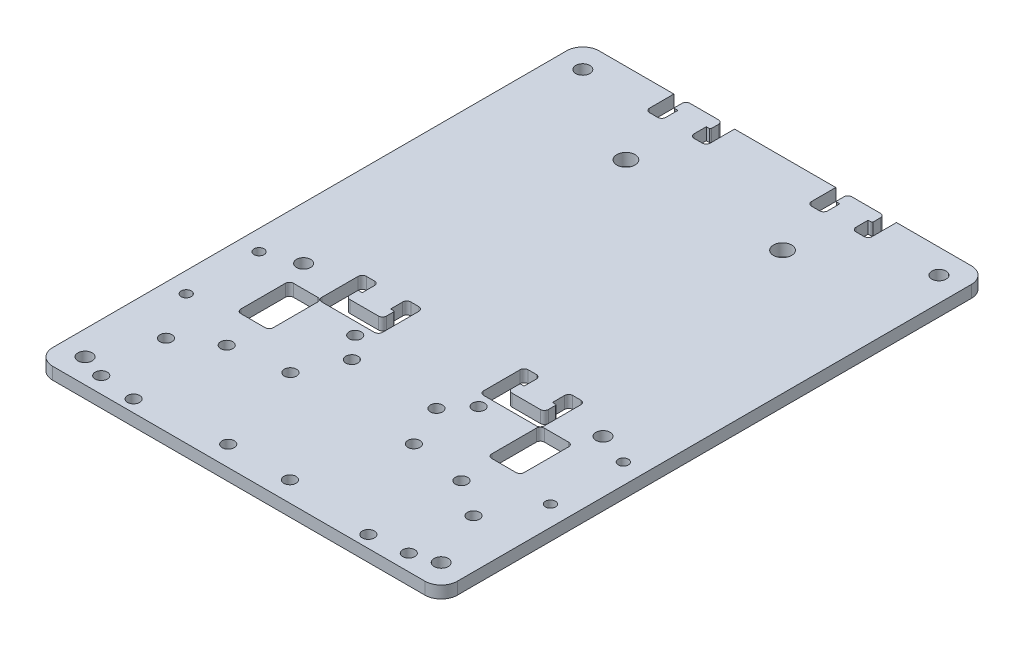
SolidWorks part; units mm, degrees
material "Acrylic (Medium-high impact)"
ref_plane "Front Plane" through (0, 0, 0) normal (0, 0, 1) x (1, 0, 0)
ref_plane "Top Plane" through (0, 0, 0) normal (0, 1, 0) x (1, 0, 0)
ref_plane "Right Plane" through (0, 0, 0) normal (1, 0, 0) x (0, 0, -1)
sketch "Sketch1" plane through (0, 0, 0) normal (0, 1, 0) x (1, 0, 0)
  line L1 (-50, 67.5) -> (50, 67.5)
  line L2 (-50, 67.5) -> (-50, -67.5)
  line L3 (-50, -67.5) -> (50, -67.5)
  line L4 (50, 67.5) -> (50, -67.5)
  line L5 (-50, 67.5) -> (50, -67.5) construction
  line L6 (-50, -67.5) -> (50, 67.5) construction
  point P0 (0, 0)
  dimension "D1" = 100
  dimension "D2" = 135
extrude "Stock" add sketch "Sketch1" against normal blind 3
fillet "base-rounds" radius 4 4 edges at (50, -1.5, 67.5) (50, -1.5, -67.5) (-50, -1.5, -67.5) (-50, -1.5, 67.5)
sketch "Sketch2" plane through (0, 0, 0) normal (0, 1, 0) x (1, 0, 0)
  line L0 (0, 0) -> (0, -62.6413) construction
  line L1 (0, 0) -> (-57.1686, 0) construction
  line L2 (-50, 63.5) -> (-50, -63.5) construction
  line L3 (-46, -67.5) -> (46, -67.5) construction
  circle A0 centre (-44, -61.5) radius 1.75
  circle A1 centre (-44, 61.5) radius 1.75
  circle A2 centre (44, -61.5) radius 1.75
  circle A3 centre (44, 61.5) radius 1.75
  circle A4 centre (-37, -14.5) radius 1.75
  circle A5 centre (37, -14.5) radius 1.75
  dimension "D3" = 3.5
  dimension "D1" = 6
  dimension "D2" = 6
  dimension "D4" = 76
  dimension "D5" = 37
extrude "holes-layers" cut sketch "Sketch2" against normal through all
sketch "Sketch4" plane through (0, 0, 0) normal (0, 1, 0) x (1, 0, 0)
  line L0 (0, 0) -> (0, -44.6235) construction
  line L5 (-46, -67.5) -> (46, -67.5) construction
  line L8 (-38, -63.5) -> (-38, -40.5) construction
  circle A0 centre (-38, -63.5) radius 1.5
  circle A1 centre (-38, -47.5) radius 1.5
  circle A4 centre (38, -47.5) radius 1.5
  circle A5 centre (38, -63.5) radius 1.5
  dimension "D2" = 3
  dimension "D1" = 4
  dimension "D3" = 16
  dimension "D4" = 76
extrude "holes-interfaceboard" cut sketch "Sketch4" against normal through all
sketch "Sketch3" plane through (0, 0, 0) normal (0, 1, 0) x (1, 0, 0)
  line L3 (-46, -67.5) -> (46, -67.5) construction
  line L4 (-45, -17.5) -> (-45, -41.9298) construction
  line L5 (-50, 63.5) -> (-50, -63.5) construction
  line L6 (45, -17.5) -> (45, -35.5) construction
  line L7 (50, -63.5) -> (50, 63.5) construction
  line L8 (-45, -17.5) -> (55.9084, -17.5) construction
  line L9 (-45, -35.5) -> (57.5, -35.5) construction
  circle A0 centre (-45, -35.5) radius 1.25
  circle A2 centre (-45, -17.5) radius 1.25
  circle A3 centre (45, -17.5) radius 1.25
  circle A4 centre (45, -35.5) radius 1.25
  dimension "D2" = 2.5
  dimension "D1" = 5
  dimension "D3" = 32
  dimension "D4" = 18
  dimension "D5" = 5
extrude "holes-motorbracket" cut sketch "Sketch3" against normal through all
sketch "Sketch11" plane through (0, 0, 0) normal (0, 1, 0) x (1, 0, 0)
  line L0 (0, 0) -> (0, -67.5) construction
  line L1 (-46, -67.5) -> (46, -67.5) construction
  line L2 (-50, -26.5) -> (50, -26.5) construction
  line L3 (-50, 63.5) -> (-50, -63.5) construction
  line L4 (50, -63.5) -> (50, 63.5) construction
  line L5 (35, -33) -> (27, -20) construction
  line L6 (-34, -20) -> (-28, -20)
  line L7 (-35, -21) -> (-35, -32)
  line L8 (-34, -33) -> (-28, -33)
  line L9 (-27, -21) -> (-27, -32)
  line L10 (-35, -20) -> (-27, -33) construction
  line L11 (-35, -33) -> (-27, -20) construction
  line L12 (35, -20) -> (27, -33) construction
  line L13 (27, -21) -> (27, -32)
  line L14 (34, -33) -> (28, -33)
  line L15 (35, -21) -> (35, -32)
  line L16 (34, -20) -> (28, -20)
  circle A0 centre (-45, -17.5) radius 1.25 construction
  circle A1 centre (-45, -35.5) radius 1.25 construction
  arc A2 (-35, -32) -> (-34, -33) centre (-34, -32) ccw
  arc A3 (-28, -33) -> (-27, -32) centre (-28, -32) ccw
  arc A4 (-27, -21) -> (-28, -20) centre (-28, -21) ccw
  arc A5 (-34, -20) -> (-35, -21) centre (-34, -21) ccw
  arc A6 (28, -33) -> (27, -32) centre (28, -32) cw
  arc A7 (34, -20) -> (35, -21) centre (34, -21) cw
  arc A8 (35, -32) -> (34, -33) centre (34, -32) cw
  arc A9 (28, -20) -> (27, -21) centre (28, -21) ccw
  point P15 (-31, -26.5)
  point P24 (31, -26.5)
  dimension "D4" = 1
  dimension "D5" = 1
  dimension "D1" = 10
  dimension "D2" = 8
  dimension "D3" = 13
extrude "holes-motorwires" cut sketch "Sketch11" against normal through all
sketch "Sketch5" plane through (0, 0, 0) normal (0, 1, 0) x (1, 0, 0)
  line L0 (-38.1711, 47.5) -> (33.6547, 47.5) construction
  line L2 (-17.1, 47.5) -> (-17.1, 39.033) construction
  line L3 (0, 56.1701) -> (0, 8.9216) construction
  line L4 (17.1, 47.5) -> (17.1, 39.033) construction
  line L5 (17.1, 39.033) -> (-17.1, 39.033) construction
  line L6 (46, 67.5) -> (-46, 67.5) construction
  circle A0 centre (-19.35, 47.5) radius 2.25
  circle A1 centre (19.35, 47.5) radius 2.25
  dimension "D4" = 4.5
  dimension "D1" = 20
  dimension "D2" = 8.467
  dimension "D3" = 34.2
  dimension "D5" = 38.7
extrude "holes-ballcaster" cut sketch "Sketch5" against normal through all
sketch "Sketch6" plane through (0, 0, 0) normal (0, 1, 0) x (1, 0, 0)
  line L0 (-7.62, -62.5) -> (7.62, -62.5) construction
  line L1 (-46, -67.5) -> (46, -67.5) construction
  line L3 (0, 0) -> (0, -67.5) construction
  circle A0 centre (-7.62, -62.5) radius 1.5
  circle A1 centre (7.62, -62.5) radius 1.5
  dimension "D4" = 3
  dimension "D1" = 5
  dimension "D5" = 15.24
extrude "holes-color/irsensor" cut sketch "Sketch6" against normal through all
ref_axis "HOLE-SENSOR" through (-7.62, -3, 62.5) along (0, 1, 0)
ref_axis "HOLE2-SENSOR" through (7.62, -3, 62.5) along (0, 1, 0)
sketch "Sketch8" plane through (0, 0, 0) normal (0, 1, 0) x (1, 0, 0)
  line L0 (0, 0) -> (0, -43.1539) construction
  line L1 (-15.5, -9.5) -> (-13.5, -9.5)
  line L2 (-26.5, -9.5) -> (-24.5, -9.5)
  line L3 (-27.5, -10.5) -> (-27.5, -19.5)
  line L4 (-26.5, -20.5) -> (-13.5, -20.5)
  line L5 (-12.5, -10.5) -> (-12.5, -19.5)
  line L6 (-27.5, -9.5) -> (-12.5, -20.5) construction
  line L7 (-27.5, -20.5) -> (-12.5, -9.5) construction
  line L9 (-23.5, -10.5) -> (-23.5, -13.5)
  line L10 (-23.5, -16.5) -> (-16.5, -16.5)
  line L11 (-16.5, -10.5) -> (-16.5, -13.5)
  line L12 (-50, 63.5) -> (-50, -63.5) construction
  line L13 (46, 67.5) -> (-46, 67.5) construction
  line L14 (-20, -15) -> (-20, -15.5037) construction
  line L24 (20, -15) -> (20, -15.5037) construction
  line L27 (-23.5, -13.5) -> (-24.25, -13.5)
  line L28 (-24.5, -15.5) -> (-24.5, -13.75)
  line L29 (-16.5, -13.5) -> (-15.75, -13.5)
  line L30 (-15.5, -15.5) -> (-15.5, -13.75)
  line L32 (27.5, -20.5) -> (12.5, -9.5) construction
  line L33 (27.5, -9.5) -> (12.5, -20.5) construction
  line L34 (15.5, -15.5) -> (15.5, -13.75)
  line L47 (16.5, -13.5) -> (15.75, -13.5)
  line L48 (24.5, -15.5) -> (24.5, -13.75)
  line L49 (23.5, -13.5) -> (24.25, -13.5)
  line L50 (16.5, -10.5) -> (16.5, -13.5)
  line L51 (23.5, -16.5) -> (16.5, -16.5)
  line L52 (23.5, -10.5) -> (23.5, -13.5)
  line L53 (12.5, -10.5) -> (12.5, -19.5)
  line L54 (26.5, -20.5) -> (13.5, -20.5)
  line L55 (27.5, -10.5) -> (27.5, -19.5)
  line L56 (26.5, -9.5) -> (24.5, -9.5)
  line L57 (15.5, -9.5) -> (13.5, -9.5)
  line L58 (-50, 25.5) -> (50, 25.5) construction
  line L59 (50, -63.5) -> (50, 63.5) construction
  line L60 (-20, 66) -> (-20, 66.5037) construction
  line L61 (-27.5, 71.5) -> (-12.5, 60.5) construction
  line L62 (-27.5, 60.5) -> (-12.5, 71.5) construction
  line L63 (-15.5, 66.5) -> (-15.5, 64.75)
  line L64 (-16.5, 64.5) -> (-15.75, 64.5)
  line L65 (-24.5, 66.5) -> (-24.5, 64.75)
  line L90 (-23.5, 64.5) -> (-24.25, 64.5)
  line L91 (-16.5, 61.5) -> (-16.5, 64.5)
  line L92 (-23.5, 67.5) -> (-16.5, 67.5)
  line L93 (-23.5, 61.5) -> (-23.5, 64.5)
  line L94 (-12.5, 61.5) -> (-12.5, 70.5)
  line L95 (-26.5, 71.5) -> (-13.5, 71.5)
  line L96 (-27.5, 61.5) -> (-27.5, 70.5)
  line L97 (-26.5, 60.5) -> (-24.5, 60.5)
  line L98 (-15.5, 60.5) -> (-13.5, 60.5)
  line L99 (27.5, 60.5) -> (12.5, 71.5) construction
  line L100 (27.5, 71.5) -> (12.5, 60.5) construction
  line L101 (20, 66) -> (20, 66.5037) construction
  line L102 (15.5, 60.5) -> (13.5, 60.5)
  line L103 (26.5, 60.5) -> (24.5, 60.5)
  line L104 (27.5, 61.5) -> (27.5, 70.5)
  line L105 (26.5, 71.5) -> (13.5, 71.5)
  line L106 (12.5, 61.5) -> (12.5, 70.5)
  line L107 (23.5, 61.5) -> (23.5, 64.5)
  line L108 (23.5, 67.5) -> (16.5, 67.5)
  line L109 (16.5, 61.5) -> (16.5, 64.5)
  line L110 (23.5, 64.5) -> (24.25, 64.5)
  line L111 (24.5, 66.5) -> (24.5, 64.75)
  line L112 (16.5, 64.5) -> (15.75, 64.5)
  line L113 (15.5, 66.5) -> (15.5, 64.75)
  arc A0 (-24.5, -9.5) -> (-23.5, -10.5) centre (-24.5, -10.5) cw
  arc A1 (-24.5, -15.5) -> (-23.5, -16.5) centre (-23.5, -15.5) ccw
  arc A2 (-16.5, -16.5) -> (-15.5, -15.5) centre (-16.5, -15.5) ccw
  arc A3 (-16.5, -10.5) -> (-15.5, -9.5) centre (-15.5, -10.5) cw
  arc A4 (-27.5, -19.5) -> (-26.5, -20.5) centre (-26.5, -19.5) ccw
  arc A5 (-13.5, -20.5) -> (-12.5, -19.5) centre (-13.5, -19.5) ccw
  arc A6 (-12.5, -10.5) -> (-13.5, -9.5) centre (-13.5, -10.5) ccw
  arc A7 (-27.5, -10.5) -> (-26.5, -9.5) centre (-26.5, -10.5) cw
  arc A8 (-15.75, -13.5) -> (-15.5, -13.75) centre (-15.75, -13.75) cw
  arc A9 (-24.5, -13.75) -> (-24.25, -13.5) centre (-24.25, -13.75) cw
  arc A20 (24.5, -13.75) -> (24.25, -13.5) centre (24.25, -13.75) ccw
  arc A21 (15.75, -13.5) -> (15.5, -13.75) centre (15.75, -13.75) ccw
  arc A22 (27.5, -10.5) -> (26.5, -9.5) centre (26.5, -10.5) ccw
  arc A23 (12.5, -10.5) -> (13.5, -9.5) centre (13.5, -10.5) cw
  arc A24 (13.5, -20.5) -> (12.5, -19.5) centre (13.5, -19.5) cw
  arc A25 (27.5, -19.5) -> (26.5, -20.5) centre (26.5, -19.5) cw
  arc A26 (16.5, -10.5) -> (15.5, -9.5) centre (15.5, -10.5) ccw
  arc A27 (16.5, -16.5) -> (15.5, -15.5) centre (16.5, -15.5) cw
  arc A28 (24.5, -15.5) -> (23.5, -16.5) centre (23.5, -15.5) cw
  arc A29 (24.5, -9.5) -> (23.5, -10.5) centre (24.5, -10.5) ccw
  arc A50 (-24.5, 64.75) -> (-24.25, 64.5) centre (-24.25, 64.75) ccw
  arc A51 (-15.75, 64.5) -> (-15.5, 64.75) centre (-15.75, 64.75) ccw
  arc A52 (-27.5, 61.5) -> (-26.5, 60.5) centre (-26.5, 61.5) ccw
  arc A53 (-12.5, 61.5) -> (-13.5, 60.5) centre (-13.5, 61.5) cw
  arc A54 (-13.5, 71.5) -> (-12.5, 70.5) centre (-13.5, 70.5) cw
  arc A55 (-27.5, 70.5) -> (-26.5, 71.5) centre (-26.5, 70.5) cw
  arc A56 (-16.5, 61.5) -> (-15.5, 60.5) centre (-15.5, 61.5) ccw
  arc A57 (-16.5, 67.5) -> (-15.5, 66.5) centre (-16.5, 66.5) cw
  arc A58 (-24.5, 66.5) -> (-23.5, 67.5) centre (-23.5, 66.5) cw
  arc A59 (-24.5, 60.5) -> (-23.5, 61.5) centre (-24.5, 61.5) ccw
  arc A60 (24.5, 60.5) -> (23.5, 61.5) centre (24.5, 61.5) cw
  arc A61 (24.5, 66.5) -> (23.5, 67.5) centre (23.5, 66.5) ccw
  arc A62 (16.5, 67.5) -> (15.5, 66.5) centre (16.5, 66.5) ccw
  arc A63 (16.5, 61.5) -> (15.5, 60.5) centre (15.5, 61.5) cw
  arc A64 (27.5, 70.5) -> (26.5, 71.5) centre (26.5, 70.5) ccw
  arc A65 (13.5, 71.5) -> (12.5, 70.5) centre (13.5, 70.5) ccw
  arc A66 (12.5, 61.5) -> (13.5, 60.5) centre (13.5, 61.5) ccw
  arc A67 (27.5, 61.5) -> (26.5, 60.5) centre (26.5, 61.5) cw
  arc A68 (15.75, 64.5) -> (15.5, 64.75) centre (15.75, 64.75) cw
  arc A69 (24.5, 64.75) -> (24.25, 64.5) centre (24.25, 64.75) cw
  point P21 (-24.5, -16.5)
  point P25 (-15.5, -16.5)
  point P46 (-15.5, -13.5)
  point P84 (15.5, -13.5)
  point P85 (15.5, -16.5)
  point P86 (24.5, -16.5)
  point P131 (-15.5, 64.5)
  point P132 (-15.5, 67.5)
  point P133 (-24.5, 67.5)
  point P172 (24.5, 67.5)
  point P173 (15.5, 67.5)
  point P174 (15.5, 64.5)
  point P175 (-25.5, -9.5)
  dimension "D8" = 1
  dimension "D10" = 0.25
  dimension "D4" = 4
  dimension "D2" = 70
  dimension "D3" = 15
  dimension "D5" = 9
  dimension "D7" = 4
  dimension "D9" = 3
  dimension "D11" = 7
  dimension "D12" = 40
extrude "straphole-powerbank" cut sketch "Sketch8" against normal through all
sketch "Sketch7" plane through (0, 0, 0) normal (0, 1, 0) x (1, 0, 0)
  line L2 (-46, -67.5) -> (46, -67.5) construction
  line L3 (-29, -64.5) -> (-29, -29.7532) construction
  line L4 (0, 0) -> (0, -53.6095) construction
  circle A0 centre (-29, -64.5) radius 1.5
  circle A4 centre (-29, -41.5) radius 1.5
  circle A5 centre (29, -64.5) radius 1.5
  circle A6 centre (29, -41.5) radius 1.5
  dimension "D3" = 3
  dimension "D1" = 3
  dimension "D2" = 23
  dimension "D4" = 58
extrude "holes-pi" cut sketch "Sketch7" against normal through all
ref_plane "BATTERY-MIDDLE" through (0, 0, -25.5) normal (0, 0, 1) x (1, 0, 0)
sketch "Sketch10" plane through (0, 0, 0) normal (0, 1, 0) x (1, 0, 0)
  line L1 (-15.25, -23.5) -> (15.25, -23.5) construction
  line L2 (15.25, -23.5) -> (15.25, -39.5) construction
  line L4 (15.25, -39.5) -> (-15.25, -39.5) construction
  line L5 (-15.25, -39.5) -> (-15.25, -23.5) construction
  line L6 (0, -19.165) -> (0, -49.8699) construction
  line L9 (-46, -67.5) -> (46, -67.5) construction
  line L10 (50, -63.5) -> (50, 63.5) construction
  line L11 (-50, 63.5) -> (-50, -63.5) construction
  circle A0 centre (-15.25, -23.5) radius 1.5
  circle A2 centre (15.25, -39.5) radius 1.5
  circle A3 centre (-15.25, -39.5) radius 1.5
  circle A4 centre (15.25, -23.5) radius 1.5
  dimension "D1" = 3
  dimension "D4" = 28
  dimension "D2" = 30.5
  dimension "D3" = 16
extrude "holes-dcdc" cut sketch "Sketch10" against normal through all
sketch "Sketch12" plane through (0, 0, 0) normal (0, 1, 0) x (1, 0, 0)
  line L0 (-38, -47.5) -> (-38, 67.5) construction
  line L2 (38, -47.5) -> (38, 67.5) construction
  line L3 (46, 67.5) -> (27.5, 67.5) construction
  line L4 (-27.5, 67.5) -> (-46, 67.5) construction
  line L5 (0, 67.5) -> (0, -67.5) construction
  line L6 (12.5, 67.5) -> (-12.5, 67.5) construction
  line L7 (-46, -67.5) -> (46, -67.5) construction
  line L8 (50, -63.5) -> (50, 63.5) construction
  line L9 (-50, 63.5) -> (-50, -63.5) construction
  circle A0 centre (-38, 61.5) radius 1.35
  circle A1 centre (38, 61.5) radius 1.35
  circle A2 centre (-38, -8.5) radius 1.35
  circle A3 centre (38, -8.5) radius 1.35
  dimension "D1" = 2.7
  dimension "D3" = 70
  dimension "D2" = 6
extrude "holes-sensorboard" [suppressed] cut sketch "Sketch12" against normal through all
ref_plane "WHEEL_CONTACT" through (0, 0, 26.5) normal (0, 0, -1) x (-1, 0, 0)
sketch "Sketch13" plane through (0, 0, 0) normal (0, 1, 0) x (1, 0, 0)
  line L1 (-50, 63.5) -> (-50, -63.5) construction
  line L2 (50, -63.5) -> (50, 63.5) construction
  line L3 (0, 66.857) -> (0, -67.5) construction
  line L4 (-46, -67.5) -> (46, -67.5) construction
  line L6 (-50, -26.5) -> (50, -26.5) construction
  circle A1 centre (-10.45, -29.12) radius 1.5
  circle A2 centre (10.45, -29.12) radius 1.5
  circle A3 centre (-45, -17.5) radius 1.25 construction
  circle A4 centre (-45, -35.5) radius 1.25 construction
  circle A7 centre (-10.45, -29.12) radius 1.5 construction
  dimension "D1" = 3
extrude "holes-IMU" cut sketch "Sketch13" against normal through all
